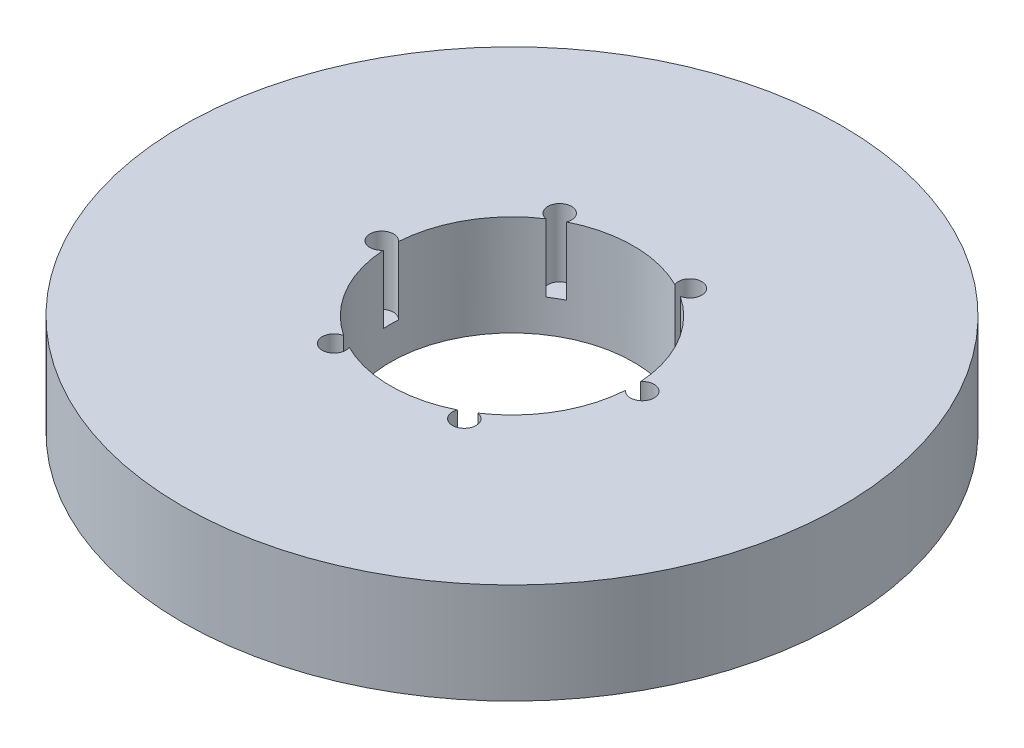
SolidWorks part; units mm, degrees
ref_plane "Front Plane" through (0, 0, 0) normal (0, 0, 1) x (1, 0, 0)
ref_plane "Top Plane" through (0, 0, 0) normal (0, 1, 0) x (1, 0, 0)
ref_plane "Right Plane" through (0, 0, 0) normal (1, 0, 0) x (0, 0, -1)
sketch "Sketch1" plane through (0, 0, 0) normal (0, 1, 0) x (1, 0, 0)
  circle A0 centre (0, 0) radius 95
  dimension "FLANGE_OD" = 190
extrude "Boss-Extrude1" add sketch "Sketch1" along normal blind 29
sketch "Sketch2" plane through (0, 0, 0) normal (0, 1, 0) x (1, 0, 0)
  circle A0 centre (0, 0) radius 35
  dimension "BORE_D" = 70
extrude "Cut-Extrude1" cut sketch "Sketch2" along normal through all
sketch "Sketch3" plane through (0, 29, 0) normal (0, 1, 0) x (1, 0, 0)
  circle A0 centre (0, 0) radius 37.5574 construction
  circle A1 centre (-37.5574, 0) radius 3.4055
  dimension "BOLT_D" = 6.8109
  dimension "BOLT_PCD" = 75.1147
extrude "Cut-Extrude2" cut sketch "Sketch3" against normal blind 19.5563
pattern_circular "CirPattern1" count 6 over 360 about axis through (0, 0, 0) along (0, 1, 0) of "Cut-Extrude2"
